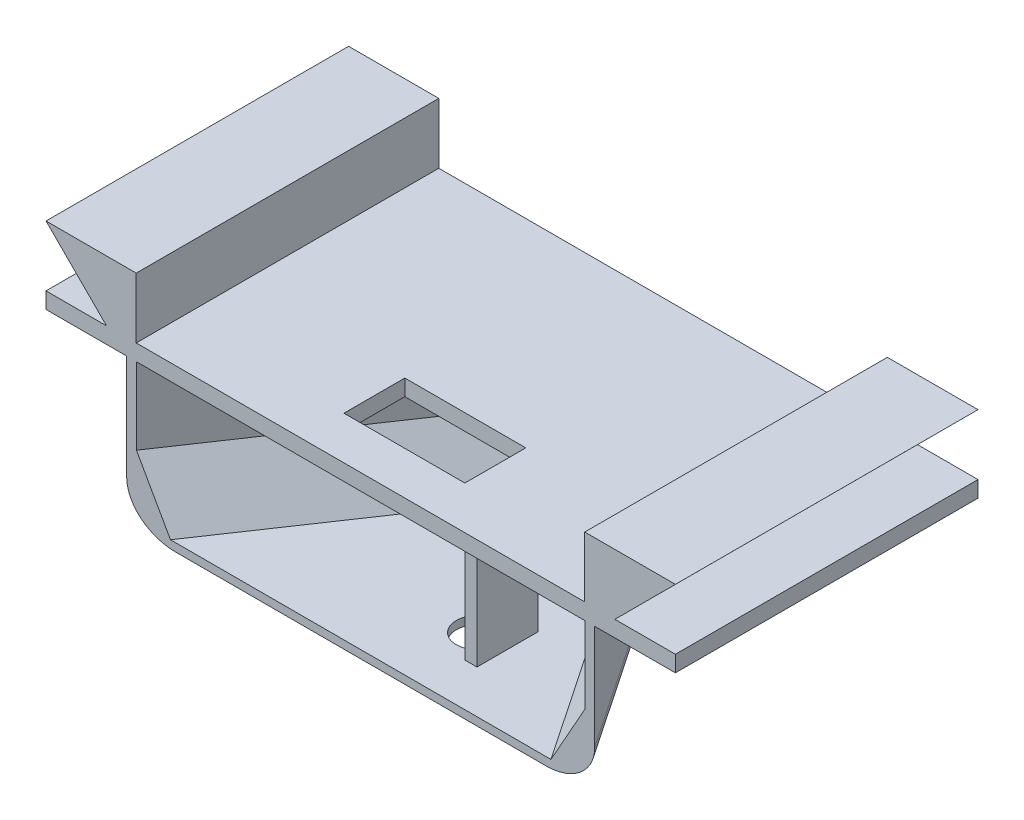
SolidWorks part; units mm, degrees
other "Camera1"
ref_plane "Front Plane" through (0, 0, 0) normal (0, 0, 1) x (1, 0, 0)
ref_plane "Top Plane" through (0, 0, 0) normal (0, 1, 0) x (1, 0, 0)
ref_plane "Right Plane" through (0, 0, 0) normal (1, 0, 0) x (0, 0, -1)
sketch "Sketch1" plane through (0, 0, 0) normal (0, 1, 0) x (1, 0, 0)
  line L0 (0, 0) -> (-116, 0)
  line L1 (-116, 0) -> (-75.5008, 60)
  line L2 (-75.5008, 60) -> (-40.5008, 60)
  line L3 (-40.5008, 60) -> (0, 0)
  dimension "D1" = 60
  dimension "D2" = 116
  dimension "D3" = 35
  dimension "D5" = 72.39
  dimension "D6" = 72.3891
extrude "Boss-Extrude1" add sketch "Sketch1" against normal blind 40
shell "Shell1" thickness 2 removed face at (-58, -20, 0)
chamfer "Chamfer3" distance 15 angle 25 2 edges at (-94.0124, -38, -29) (-21.9884, -38, -29) first distance on face at (-94.0124, -20, -29) first distance on face at (-21.9884, -20, -29)
fillet "Fillet1" radius 10 2 edges at (-20.2504, -40, -30) (-95.7504, -40, -30)
fillet "Fillet2" radius 5 5 edges at (-40.5008, -15, -60) (-44.0345, -37.0711, -60) (-75.5008, -15, -60) (-71.9671, -37.0711, -60) (-58.0008, -40, -60)
sketch "Sketch12" plane through (0, -40, 0) normal (0, -1, 0) x (-1, 0, 0)
  circle A0 centre (47.2011, 18.0841) radius 5.2
sketch "Sketch13" plane through (0, -2, 0) normal (0, -1, 0) x (1, 0, 0)
  line L1 (-39.8423, -25.7584) -> (-42.8423, -25.7584)
  line L2 (-39.8423, -25.7584) -> (-39.8423, -10.6584)
  line L3 (-39.8423, -10.6584) -> (-42.8423, -10.6584)
  line L4 (-42.8423, -25.7584) -> (-42.8423, -10.6584)
  dimension "D1" = 3
extrude "Boss-Extrude3" add sketch "Sketch13" along normal blind 36
extrude "Cut-Extrude12" cut sketch "Sketch12" against normal blind 9
sketch "Sketch15" plane through (0, 0, 0) normal (0, 1, 0) x (1, 0, 0)
  line L8 (-136, 75) -> (20, 75)
  line L9 (20, 0) -> (20, 75)
  line L10 (20, 0) -> (-136, 0)
  line L11 (-136, 0) -> (-136, 75)
extrude "Boss-Extrude7" add sketch "Sketch15" along normal blind 15
sketch "Sketch16" plane through (0, 0, 0) normal (0, 0, 1) x (1, 0, 0)
  line L8 (20, 15) -> (20, 0)
  line L9 (20, 0) -> (5.0045, 0)
  line L10 (0, 0) -> (20, 0) construction
  line L11 (5.0045, 0) -> (20, 15)
extrude "Cut-Extrude14" cut sketch "Sketch16" against normal blind 75
sketch "Sketch17" plane through (0, 0, 0) normal (0, 0, 1) x (1, 0, 0)
  line L0 (-136, 15) -> (-136, 0)
  line L1 (-136, 0) -> (-121.0045, 0)
  line L2 (-136, 0) -> (-116, 0) construction
  line L3 (-121.0045, 0) -> (-136, 15)
extrude "Cut-Extrude15" cut sketch "Sketch17" against normal blind 75
sketch "Sketch18" plane through (0, 0, 0) normal (0, -1, 0) x (1, 0, 0)
  line L0 (-116, 0) -> (-121.0045, 0)
  line L1 (-121.0045, 0) -> (-136.0045, 0)
  line L2 (-136.0045, 0) -> (-136.0045, -75)
  line L3 (-136.0045, -75) -> (-121.0045, -75)
  line L5 (20.0045, -75) -> (20.0045, 0)
  line L6 (20.0045, 0) -> (-116, 0)
  line L7 (20.0045, -75) -> (5.0045, -75)
  line L8 (-121.0045, -75) -> (5.0045, -75)
extrude "Boss-Extrude8" add sketch "Sketch18" along normal blind 4 contours L8 L7 L5 L6 L0 L1 L2 L3
sketch "Sketch20" plane through (0, -4, 0) normal (0, -1, 0) x (-1, 0, 0)
  line L1 (42.8423, 25.7584) -> (72.8207, 25.7584)
  line L2 (42.8423, 25.7584) -> (42.8423, 10.6584)
  line L3 (42.8423, 10.6584) -> (72.8207, 10.6584)
  line L4 (72.8207, 25.7584) -> (72.8207, 10.6584)
extrude "Cut-Extrude17" cut sketch "Sketch20" against normal blind 39 contours L2 L1 L4 L3
sketch "Sketch26" plane through (-42.8423, 0, 0) normal (-1, 0, 0) x (0, 0, 1)
  line L6 (-10.6584, -38) -> (-18.2084, -38)
  line L7 (-10.6584, -38) -> (-10.6584, -10.7935)
  line L8 (-10.6584, -10.7935) -> (-18.2084, -10.7935)
  line L9 (-18.2084, -38) -> (-18.2084, -10.7935)
sketch "Sketch29" plane through (-42.8423, 0, 0) normal (-1, 0, 0) x (0, 0, 1)
  circle A0 centre (-18.2084, -10.7935) radius 2.1
extrude "Cut-Extrude22" cut sketch "Sketch29" against normal blind 10 contours A0
sketch "Sketch32" plane through (0, 0, -58) normal (0, 0, 1) x (1, 0, 0)
sketch "Sketch33" plane through (0, 0, -58) normal (0, 0, 1) x (1, 0, 0)
sketch "Sketch34" plane through (0, 0, -58) normal (0, 0, 1) x (1, 0, 0)
  line L0 (-74.4378, -23) -> (-74.4378, -4) construction
  line L1 (-53.7528, -25.65) -> (-62.2528, -25.65)
  line L2 (-53.7528, -25.65) -> (-53.7528, -17.15)
  line L3 (-53.7528, -17.15) -> (-62.2528, -17.15)
  line L4 (-62.2528, -25.65) -> (-62.2528, -17.15)
  line L10 (-41.5637, -4) -> (-74.4378, -4) construction
  circle A0 centre (-68.5028, -21.5) radius 1.1
  circle A1 centre (-68.5028, -9) radius 1.1
  dimension "D5" = 6.25
  dimension "D6" = 17.5
  dimension "D7" = 6.25
  dimension "D8" = 5
  dimension "D1" = 12.185
  dimension "D2" = 8.5
  dimension "D3" = 8.5
  dimension "D4" = 13.15
extrude "Cut-Extrude23" cut sketch "Sketch34" against normal blind 10
sketch "Sketch35" plane through (0, 0, -58) normal (0, 0, 1) x (1, 0, 0)
  line L0 (-53.7528, -25.65) -> (-53.7528, -17.15) construction
  line L1 (-41.5637, -4) -> (-74.4378, -4) construction
  circle A0 centre (-47.5028, -21.5) radius 1.1
  circle A1 centre (-47.5028, -9) radius 1.1
  dimension "D1" = 6.25
  dimension "D2" = 17.5
  dimension "D3" = 6.25
  dimension "D4" = 5
extrude "Cut-Extrude24" cut sketch "Sketch35" against normal blind 10
sketch "Sketch36" plane through (0, 0, 0) normal (0, 0, 1) x (1, 0, 0)
  line L0 (-136, 15) -> (20, 15) construction
  line L1 (-2.4692, 15) -> (-113.6392, 15)
  line L2 (-2.4692, 15) -> (-2.4692, 0)
  line L3 (-2.4692, 0) -> (-113.6392, 0)
  line L4 (-113.6392, 15) -> (-113.6392, 0)
ref_plane "Plane19" through (-113.587, -4, 0) normal (-1, 0, 0) x (0, 0, 1)
extrude "Cut-Extrude25" cut sketch "Sketch36" against normal blind 85 contours L2 L1 L4 L3
